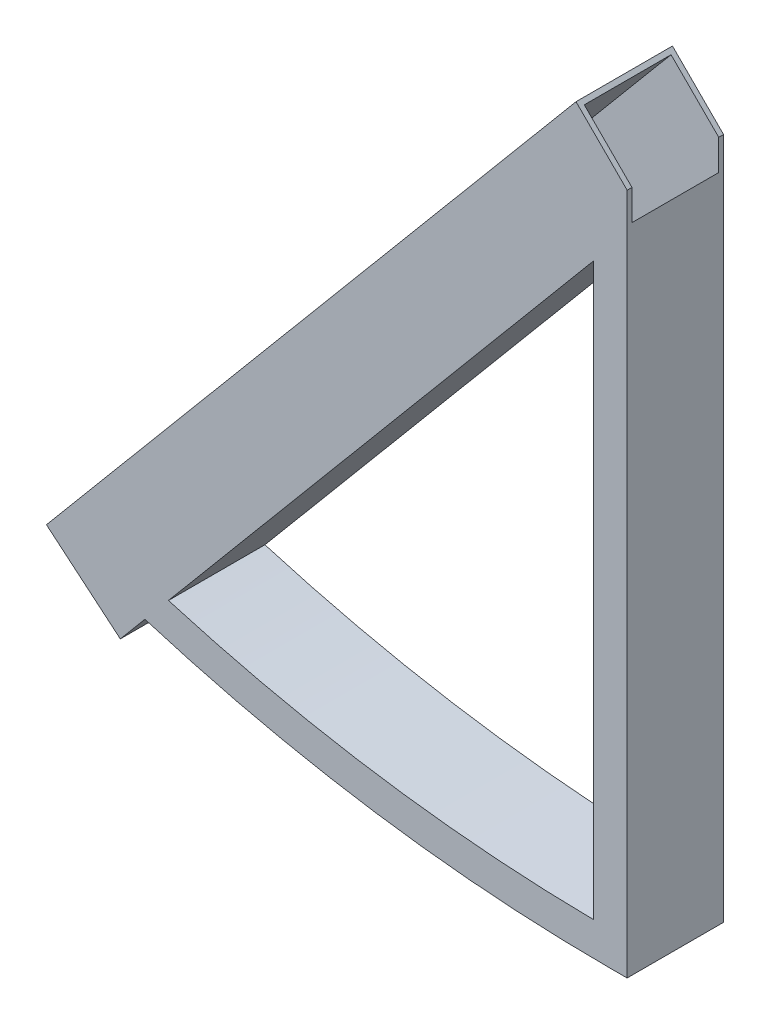
SolidWorks part; units mm, degrees
ref_plane "Front Plane" through (0, 0, 0) normal (0, 0, 1) x (1, 0, 0)
ref_plane "Top Plane" through (0, 0, 0) normal (0, 1, 0) x (1, 0, 0)
ref_plane "Right Plane" through (0, 0, 0) normal (1, 0, 0) x (0, 0, -1)
sketch "Sketch1" plane through (0, 0, 0) normal (0, 0, 1) x (1, 0, 0)
  line L0 (-3.5, 7) -> (-3.5, 125.2716)
  line L1 (0, 0) -> (145, 0) construction
  line L2 (145, 0) -> (0, 145) construction
  line L3 (0, 145) -> (-109.2739, 14.7724) construction
  line L5 (-7.0981, 152.0981) -> (-116.9343, 21.2003)
  line L6 (-116.9343, 21.2003) -> (-101.6134, 8.3446)
  line L7 (-101.6134, 8.3446) -> (-96.5092, 14.4276)
  line L9 (3.5, 141.5) -> (3.5, 0)
  line L10 (3.5, 0) -> (0, 0)
  line L11 (-91.625, 20.2483) -> (-3.5, 125.2716)
  line L13 (-3.5, 125.2716) -> (-18.8209, 138.1274) construction
  line L14 (3.5, 141.5) -> (-7.0981, 152.0981)
  line L15 (-3.5, 7) -> (3.5, 7) construction
  line L16 (0, 7) -> (0, 0) construction
  line L17 (3.5, 0) -> (-3.5, 0) construction
  line L18 (-3.5, 0) -> (-3.5, 7) construction
  arc A0 (0, 0) -> (-96.5092, 14.4276) centre (0, 330) cw
  arc A1 (-91.625, 20.2483) -> (-3.5, 7) centre (0, 330) ccw
  dimension "D2" = 330
  dimension "D1" = 145
  dimension "D3" = 50
  dimension "D4" = 20
  dimension "D6" = 45
  dimension "D7" = 7
  dimension "D8" = 145
  dimension "D9" = 170
extrude "Boss-Extrude1" add sketch "Sketch1" along normal blind 10 and the other way blind 10
sketch "Sketch2" plane through (-37.8753, -45.1381, 0) normal (-0.6428, -0.766, 0) x (-0.766, 0.6428, 0)
  line L0 (103.2042, -10) -> (83.2042, 10) construction
  line L1 (83.2042, -10) -> (103.2042, 10) construction
  line L3 (102.2042, 9) -> (84.2042, 9)
  line L4 (83.2042, 10) -> (83.2042, -10)
  line L5 (83.2042, -10) -> (103.2042, -10)
  line L6 (103.2042, -10) -> (103.2042, 10)
  line L7 (103.2042, 10) -> (83.2042, 10)
  line L8 (83.2042, 10) -> (83.2042, -10) construction
  line L9 (83.2042, -10) -> (103.2042, -10) construction
  line L10 (103.2042, -10) -> (103.2042, 10) construction
  line L11 (103.2042, 10) -> (83.2042, 10) construction
  line L12 (102.2042, 9) -> (102.2042, -9)
  line L13 (102.2042, -9) -> (84.2042, -9)
  line L14 (84.2042, 9) -> (84.2042, -9)
  line L15 (102.2042, 9) -> (84.2042, -9) construction
  line L16 (102.2042, -9) -> (84.2042, 9) construction
  point P2 (93.2042, 0)
  dimension "D2" = 18
  dimension "D1" = 0
extrude "Cut-Extrude1" cut sketch "Sketch2" against normal through all both and the other way through all
